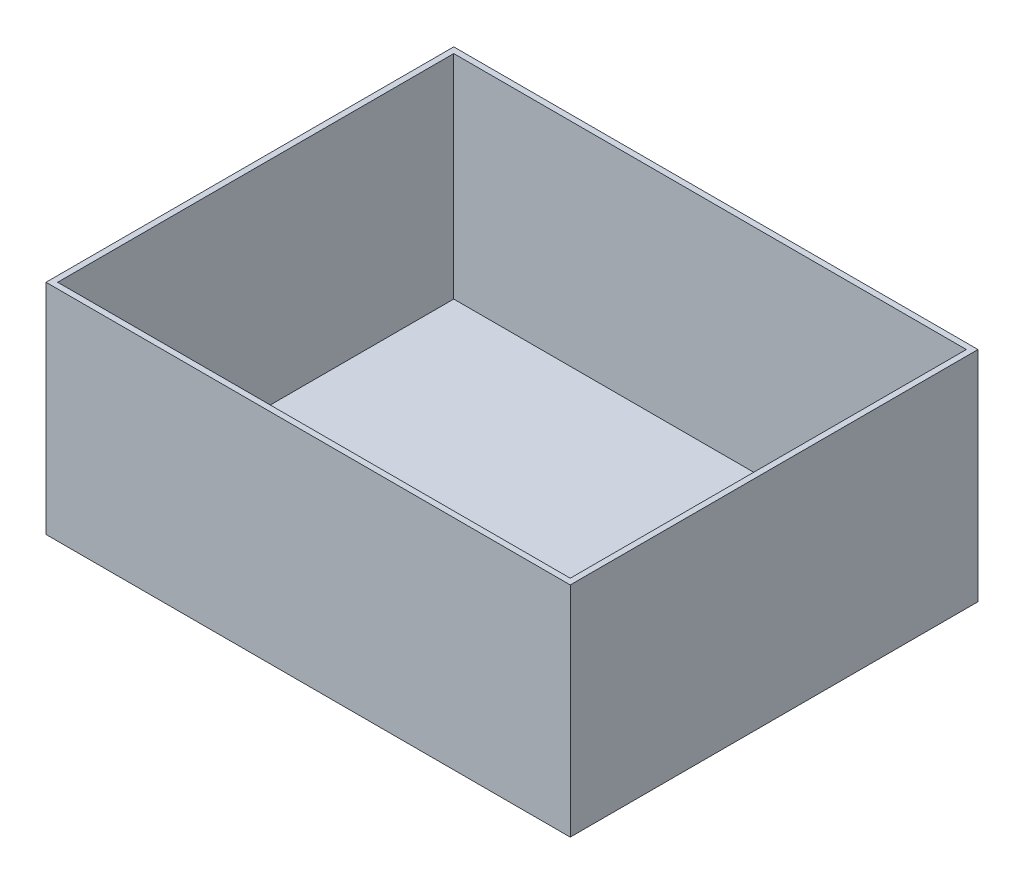
SolidWorks part; units mm, degrees
ref_plane "Front Plane" through (0, 0, 0) normal (0, 0, 1) x (1, 0, 0)
ref_plane "Top Plane" through (0, 0, 0) normal (0, 1, 0) x (1, 0, 0)
ref_plane "Right Plane" through (0, 0, 0) normal (1, 0, 0) x (0, 0, -1)
sketch "Sketch2" plane through (0, 0, 0) normal (0, 1, 0) x (1, 0, 0)
  line L1 (-114.3, 88.9) -> (114.3, 88.9)
  line L2 (-114.3, 88.9) -> (-114.3, -88.9)
  line L3 (-114.3, -88.9) -> (114.3, -88.9)
  line L4 (114.3, 88.9) -> (114.3, -88.9)
  line L5 (-114.3, 88.9) -> (114.3, -88.9) construction
  line L6 (-114.3, -88.9) -> (114.3, 88.9) construction
  point P0 (0, 0)
  dimension "D1" = 177.8
  dimension "D2" = 228.6
extrude "Boss-Extrude1" add sketch "Sketch2" along normal blind 95.25
shell "Shell3" thickness 2.54 removed face at (0, 95.25, 0)
